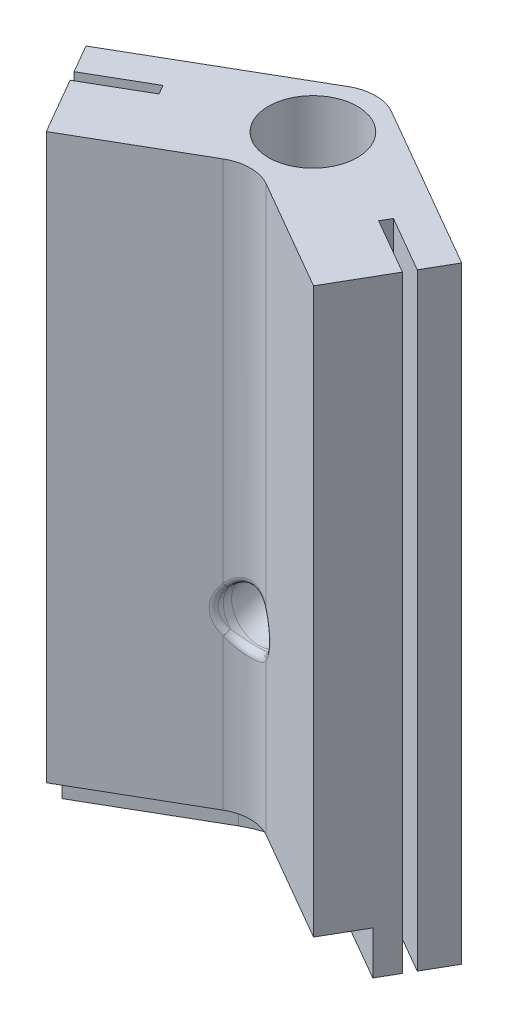
SolidWorks part; units mm, degrees
ref_plane "Front Plane" through (0, 0, 0) normal (0, 0, 1) x (1, 0, 0)
ref_plane "Top Plane" through (0, 0, 0) normal (0, 1, 0) x (1, 0, 0)
ref_plane "Right Plane" through (0, 0, 0) normal (1, 0, 0) x (0, 0, -1)
sketch "Sketch1" plane through (0, 0, 0) normal (0, 1, 0) x (1, 0, 0)
  line L0 (0, -153.0167) -> (0, 58.3538) construction
  line L1 (97.0301, 0) -> (-101.5537, 0) construction
  line L2 (-10, -5.7735) -> (-86.6025, -50)
  line L3 (10, -5.7735) -> (86.6025, -50)
  line L4 (10, -63.5085) -> (61.6025, -93.3013)
  line L5 (-10, -63.5085) -> (-61.6025, -93.3013)
  line L6 (86.6025, -50) -> (61.6025, -93.3013) construction
  line L7 (-86.6025, -50) -> (-61.6025, -93.3013) construction
  line L8 (86.6025, -50) -> (79.1025, -62.9904)
  line L9 (79.1025, -62.9904) -> (53.1218, -47.9904)
  line L10 (53.1218, -47.9904) -> (50.6218, -52.3205)
  line L11 (50.6218, -52.3205) -> (76.6025, -67.3205)
  line L12 (76.6025, -67.3205) -> (61.6025, -93.3013)
  line L13 (-86.6025, -50) -> (-79.1025, -62.9904)
  line L14 (-79.1025, -62.9904) -> (-53.1218, -47.9904)
  line L15 (-53.1218, -47.9904) -> (-50.6218, -52.3205)
  line L16 (-50.6218, -52.3205) -> (-76.6025, -67.3205)
  line L17 (-76.6025, -67.3205) -> (-61.6025, -93.3013)
  circle A0 centre (0, -32) radius 20.5 construction
  arc A1 (10, -63.5085) -> (-10, -63.5085) centre (0, -80.829) ccw
  arc A2 (-10, -5.7735) -> (10, -5.7735) centre (0, -23.094) cw
  point P21 (0, -30.9248)
  point P24 (0, -57.735)
  point P27 (0, 0)
  dimension "D9" = 41
  dimension "D10" = 20
  dimension "D1" = 30
  dimension "D2" = 30
  dimension "D3" = 50
  dimension "D4" = 90
  dimension "D5" = 90
  dimension "D6" = 100
  dimension "D7" = 5
  dimension "D8" = 30
  dimension "D11" = 32
  dimension "D12" = 15
extrude "Boss-Extrude1" add sketch "Sketch1" along normal blind 280
sketch "Sketch3" plane through (0, 280, 0) normal (0, 1, 0) x (1, 0, 0)
  line L0 (0, 17.6251) -> (0, -106.1965) construction
  line L1 (97.0301, 0) -> (-101.5537, 0) construction
  line L2 (97.0301, 0) -> (-101.5537, 0) construction
  circle A0 centre (0, -32) radius 20.5 construction
  circle A1 centre (0, -32) radius 20.5
extrude "Cut-Extrude1" cut sketch "Sketch3" against normal blind 100
sketch "Sketch4" plane through (0, 0, 0) normal (1, 0, 0) x (0, 0, -1)
  line L0 (-11.5, 180) -> (-52.5, 180) construction
  line L1 (-11.5, 180) -> (-52.5, 180) construction
  line L2 (-60.829, 0) -> (-60.829, 280) construction
  line L3 (-60.829, 0) -> (-60.829, 280) construction
  line L4 (-32, 180) -> (-32, 125)
  line L5 (-57, 100) -> (-60.829, 100)
  line L6 (-60.829, 100) -> (-80.829, 100)
  arc A0 (-32, 125) -> (-57, 100) centre (-57, 125) cw
  dimension "D2" = 25
  dimension "D1" = 80
  dimension "D3" = 20
sweep "Cut-Sweep1" cut path "Sketch4" circular profile diameter 25 parameters "D3"=25
fillet "Fillet1" radius 3 6 edges at (3.7372, 88.0718, 61.1813) (-6.8903, 89.5705, 62.0534) (-12.5, 100, 64.9519) (-4.6494, 111.6032, 61.377) (6.8903, 110.4295, 62.0534) (12.5, 100, 64.9519)
sketch "Sketch18" plane through (0, 0, 0) normal (0, -1, 0) x (1, 0, 0)
  line L1 (10, 63.5085) -> (61.6025, 93.3013) construction
  line L3 (-61.6025, 93.3013) -> (-10, 63.5085) construction
  line L4 (-71.6025, 75.9808) -> (-20, 46.188)
  line L5 (10, 63.5085) -> (61.6025, 93.3013)
  line L6 (20, 46.188) -> (71.6025, 75.9808)
  line L7 (-61.6025, 93.3013) -> (-10, 63.5085)
  line L8 (-71.6025, 75.9808) -> (-61.6025, 93.3013)
  line L9 (71.6025, 75.9808) -> (61.6025, 93.3013)
  arc A0 (-10, 63.5085) -> (10, 63.5085) centre (0, 80.829) ccw construction
  arc A1 (-10, 63.5085) -> (10, 63.5085) centre (0, 80.829) ccw
  arc A2 (-20, 46.188) -> (20, 46.188) centre (0, 80.829) ccw
  dimension "D1" = 20
extrude "Cut-Extrude2" cut sketch "Sketch18" against normal blind 20
